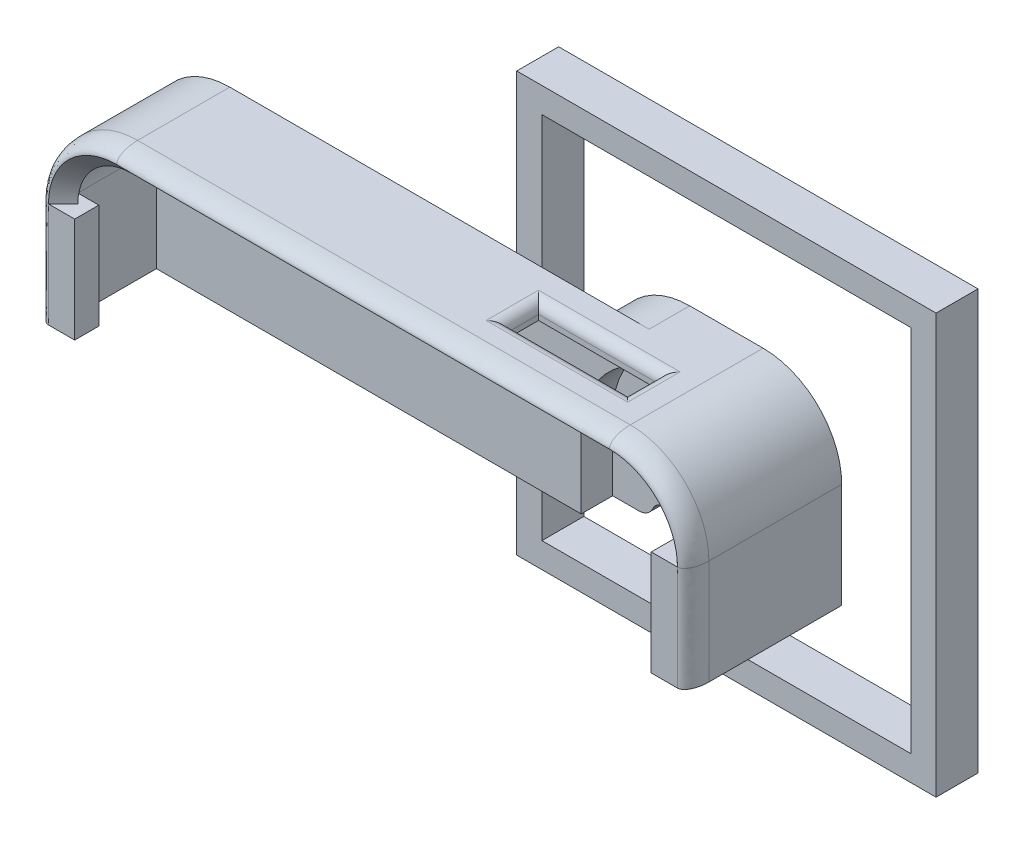
SolidWorks part; units mm, degrees
ref_plane "Front Plane" through (0, 0, 0) normal (0, 0, 1) x (1, 0, 0)
ref_plane "Top Plane" through (0, 0, 0) normal (0, 1, 0) x (1, 0, 0)
ref_plane "Right Plane" through (0, 0, 0) normal (1, 0, 0) x (0, 0, -1)
sketch "Sketch1" plane through (0, 0, 0) normal (0, 0, 1) x (1, 0, 0)
  line L0 (31, 17.5) -> (31, 0)
  line L1 (0, 0) -> (62, 0)
  line L2 (0, 0) -> (0, 10)
  line L3 (7.5, 17.5) -> (54.5, 17.5)
  line L4 (62, 0) -> (62, 10)
  line L5 (7.5, 16) -> (54.5, 16)
  line L9 (1.5, 0) -> (1.5, 10)
  line L12 (60.5, 10) -> (60.5, 0)
  arc A0 (0, 10) -> (7.5, 17.5) centre (7.5, 10) cw
  arc A1 (62, 10) -> (54.5, 17.5) centre (54.5, 10) ccw
  arc A2 (1.5, 10) -> (7.5, 16) centre (7.5, 10) cw
  arc A3 (60.5, 10) -> (54.5, 16) centre (54.5, 10) ccw
  dimension "D5" = 1.5
extrude "Boss-Extrude1" add sketch "Sketch1" along normal blind 10.8 contours L9 A2 L5 L0 L3 A0 L2 L1 | A3 L12 L1 L4 A1 L3 L0 L5 region at (42.75, 17.144, 0) region at (30.644, 16.75, 0)
sketch "Sketch2" plane through (0, 0, 0) normal (0, 0, -1) x (-1, 0, 0)
  line L0 (-1.5, 0) -> (-1.5, 10)
  line L1 (-7.5, 16) -> (-54.5, 16)
  line L2 (-60.5, 0) -> (-60.5, 10)
  line L3 (-60.5, 0) -> (-1.5, 0)
  arc A0 (-1.5, 10) -> (-7.5, 16) centre (-7.5, 10) ccw
  arc A1 (-54.5, 16) -> (-60.5, 10) centre (-54.5, 10) ccw
extrude "Boss-Extrude2" add sketch "Sketch2" against normal blind 1 separate body
combine bodies "Combine1" operation type add bodies to combine 102 101
sketch "Sketch3" plane through (0, 0, 10.8) normal (0, 0, 1) x (1, 0, 0)
  line L0 (0, 0) -> (3.5, 0)
  line L1 (0, 0) -> (0, 10)
  line L2 (0, 0) -> (0, 10) construction
  line L3 (3.5, 0) -> (3.5, 10)
  line L4 (3.5, 10) -> (0, 10)
  line L5 (1.5, 10) -> (1.5, 0)
  line L6 (31, 16) -> (31, -7.5027)
  line L7 (7.5, 16) -> (54.5, 16) construction
  line L8 (60.5, 10) -> (60.5, 0)
  line L9 (62, 0) -> (58.5, 0)
  line L10 (58.5, 10) -> (62, 10)
  line L11 (58.5, 0) -> (58.5, 10)
  line M7 (1.5, 0) -> (1.5, 10)
  line M11 (60.5, 10) -> (60.5, 0)
  dimension "D1" = 3.5
  dimension "D2" = 10
extrude "Boss-Extrude3" add sketch "Sketch3" against normal blind 2.3 contours L3 L4 L0 M7 | L11 L9 L10 M11 region at (2.5, 5, 10.8) region at (59.5, 5, 10.8)
fillet "Fillet1" radius 1 5 edges at (0, 5, 10.8) (62, 5, 10.8) (2.1967, 15.3033, 10.8) (59.8033, 15.3033, 10.8) (31, 17.5, 10.8) second distance 2 first distance on face at (31, 9.4708, 10.8)
sketch "Sketch4" plane through (0, 17.5, 0) normal (0, 1, 0) x (1, 0, 0)
  line L0 (62, -8.8) -> (62, 0) construction
  line L1 (51.5, -6.05) -> (40, -6.05)
  line L2 (51.5, -6.05) -> (51.5, -3.05)
  line L3 (51.5, -3.05) -> (40, -3.05)
  line L4 (40, -6.05) -> (40, -3.05)
  line L5 (7.5, 0) -> (54.5, 0) construction
  dimension "D1" = 10.5
  dimension "D2" = 11.5
  dimension "D3" = 3.05
  dimension "D4" = 3
extrude "Cut-Extrude1" cut sketch "Sketch4" against normal up to next
sketch "Sketch5" plane through (0, 0, 10.8) normal (0, 0, 1) x (1, 0, 0)
  line L1 (7.5, 15) -> (54.5, 15)
  line L2 (7.5, 16) -> (54.5, 16) construction
  line L4 (3.5, 10) -> (1.5, 10) construction
  line L5 (31, 16.5) -> (31, -2.3238) construction
  line L6 (54.5, 16.5) -> (7.5, 16.5) construction
  line L7 (59.5, 10) -> (60.5, 10)
  line L8 (54.5, 16) -> (7.5, 16)
  line L9 (1.5, 10) -> (2.5, 10)
  arc A1 (2.5, 10) -> (7.5, 15) centre (7.5, 10) cw
  arc A2 (59.5, 10) -> (54.5, 15) centre (54.5, 10) ccw
  arc A3 (60.5, 10) -> (54.5, 16) centre (54.5, 10) ccw
  arc A4 (7.5, 16) -> (1.5, 10) centre (7.5, 10) ccw
  dimension "D1" = 1
extrude "Boss-Extrude4" add sketch "Sketch5" against normal blind 2.3
chamfer "Chamfer1" distance 1.5 angle 45 3 edges at (58.0355, 13.5355, 10.8) (31, 15, 10.8) (3.9645, 13.5355, 10.8)
chamfer "Chamfer3" distance 1 angle 45 3 edges at (58.0355, 13.5355, 8.5) (31, 15, 8.5) (3.9645, 13.5355, 8.5)
sketch "Sketch6" plane through (0, 0, 0) normal (0, 0, -1) x (-1, 0, 0)
  line L0 (-59.98, 0) -> (-59.98, 6.7)
  line L1 (-59.98, 0) -> (-42.02, 0)
  line L2 (-42.02, 0) -> (-42.02, 6.7)
  arc A0 (-42.02, 6.7) -> (-59.98, 6.7) centre (-51, 6.7) ccw
extrude "Cut-Extrude2" cut sketch "Sketch6" against normal blind 2
sketch "Sketch9" plane through (0, 0, 0) normal (0, 0, -1) x (-1, 0, 0)
  line L0 (-62, 10) -> (-62, 0)
  line L1 (-62, 0) -> (-59.98, 0)
  line L2 (-59.98, 0) -> (-59.98, 6.7)
  line L3 (-42.02, 6.7) -> (-42.02, 0)
  line L4 (-42.02, 0) -> (-40, 0)
  line L5 (-42.02, 0) -> (0, 0) construction
  line L6 (-40, 0) -> (-40, 10)
  line L8 (-54.5, 17.5) -> (-47.5, 17.5)
  arc A0 (-59.98, 6.7) -> (-42.02, 6.7) centre (-51, 6.7) cw
  arc A1 (-47.5, 17.5) -> (-40, 10) centre (-47.5, 10) cw
  arc A2 (-54.5, 17.5) -> (-62, 10) centre (-54.5, 10) ccw
extrude "Boss-Extrude6" add sketch "Sketch9" along normal blind 2
fillet "Fillet2" radius 1 4 edges at (45.75, 17.5, 3.05) (51.5, 17.5, 4.55) (45.75, 17.5, 6.05) (40, 17.5, 4.55)
sketch "Sketch10" plane through (0, 0, -2) normal (0, 0, -1) x (-1, 0, 0)
  line L0 (-62, 10) -> (-62, 0)
  line L1 (-62, 0) -> (-40, 0)
  line L2 (-40, 0) -> (-40, 10)
  line L3 (-54.5, 17.5) -> (-47.5, 17.5)
  arc A0 (-62, 10) -> (-54.5, 17.5) centre (-54.5, 10) cw
  arc A1 (-40, 10) -> (-47.5, 17.5) centre (-47.5, 10) ccw
extrude "Boss-Extrude7" add sketch "Sketch10" along normal blind 1.87
sketch "Sketch11" plane through (0, 0, -2) normal (0, 0, 1) x (1, 0, 0)
  circle A0 centre (51, 8.65) radius 2.5
  dimension "D1" = 5
extrude "Cut-Extrude3" cut sketch "Sketch11" against normal through all
sketch "Sketch19" plane through (0, 0, 0) normal (0, -1, 0) x (1, 0, 0)
  line L0 (59.98, -2) -> (42.02, -2) construction
  line L1 (56, -2) -> (46, -2)
  line L2 (56, -2) -> (56, -3.87)
  line L3 (56, -3.87) -> (46, -3.87)
  line L4 (46, -2) -> (46, -3.87)
  line L5 (62, -3.87) -> (40, -3.87) construction
  line L6 (62, 8.8) -> (62, -3.87) construction
  dimension "D1" = 10
  dimension "D2" = 6
extrude "Cut-Extrude5" cut sketch "Sketch19" against normal blind 1.5
fillet "Fillet7" radius 1.5 2 edges at (46, 0, -2.935) (56, 0, -2.935)
fillet "Fillet8" radius 1 2 edges at (46, 1.5, -2.935) (56, 1.5, -2.935)
sketch "Sketch20" plane through (0, 0, -3.87) normal (0, 0, -1) x (-1, 0, 0)
  line L0 (-51, 28.65) -> (-51, -11.35) construction
  line L1 (-71, 28.65) -> (-31, 28.65)
  line L2 (-71, 28.65) -> (-71, -11.35)
  line L3 (-71, -11.35) -> (-31, -11.35)
  line L4 (-31, 28.65) -> (-31, -11.35)
  line L5 (-71, 8.65) -> (-31, 8.65) construction
  line L7 (-68.6, 26.25) -> (-33.4, 26.25)
  line L8 (-68.6, 26.25) -> (-68.6, -8.95)
  line L9 (-68.6, -8.95) -> (-33.4, -8.95)
  line L10 (-33.4, 26.25) -> (-33.4, -8.95)
  circle A0 centre (-51, 8.65) radius 2.5 construction
  dimension "D1" = 40
  dimension "D2" = 40
  dimension "D3" = 0
  dimension "D4" = 0
  dimension "D5" = 35.2
  dimension "D6" = 35.2
  dimension "D7" = 17.6
  dimension "D8" = 17.6
extrude "Boss-Extrude8" add sketch "Sketch20" along normal blind 4 separate body
